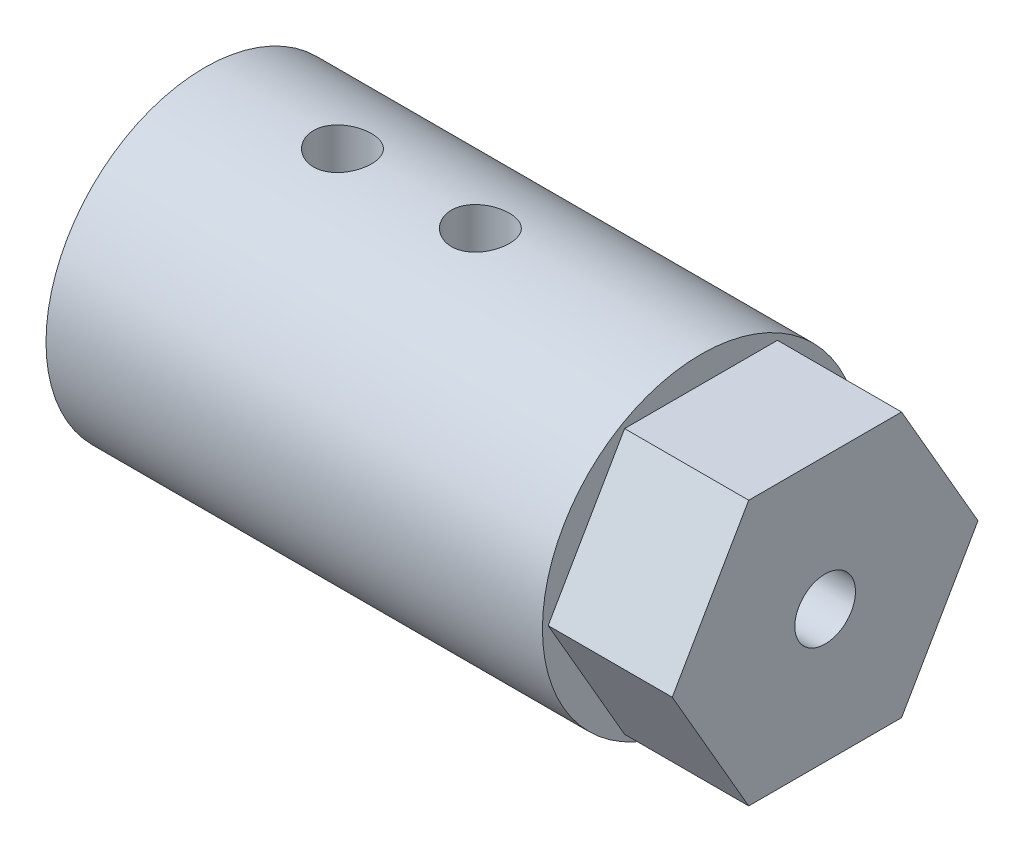
SolidWorks part; units mm, degrees
material "PLA2"
ref_plane "Front Plane" through (0, 0, 0) normal (0, 0, 1) x (1, 0, 0)
ref_plane "Top Plane" through (0, 0, 0) normal (0, 1, 0) x (1, 0, 0)
ref_plane "Right Plane" through (0, 0, 0) normal (1, 0, 0) x (0, 0, -1)
sketch "Sketch1" plane through (0, 0, 0) normal (1, 0, 0) x (0, 0, -1)
  line L0 (0, 0) -> (50000, 0) construction
  line L1 (-3.5195, 6.096) -> (3.5195, 6.096)
  line L2 (3.5195, 6.096) -> (7.0391, 0)
  line L3 (0, 0) -> (0, 50000) construction
  line L4 (-3.5195, 6.096) -> (-7.0391, 0)
  line L5 (-3.5195, -6.096) -> (-7.0391, 0)
  line L6 (3.5195, -6.096) -> (7.0391, 0)
  line L7 (-3.5195, -6.096) -> (3.5195, -6.096)
  point P8 (0, 6.096)
  point P13 (0, -6.096)
  dimension "D1" = 12.192
  dimension "D2" = 12.192
extrude "Hex" add sketch "Sketch1" along normal blind 5.715
sketch "Sketch2" plane through (0, 0, 0) normal (-1, 0, 0) x (0, 0, 1)
  circle A0 centre (0, 0) radius 7.3025
  circle A1 centre (0, 0) radius 3.2766
  dimension "D1" = 6.5532
  dimension "D2" = 14.605
extrude "Rotary_Shaft" add sketch "Sketch2" along normal blind 22.86
fillet "Fillet1" [suppressed] radius 0.889
fillet "Fillet2" [suppressed] radius 0.508
fillet "Fillet3" [suppressed] radius 0.508
sketch "Sketch3" plane through (0, 0, 0) normal (0, 1, 0) x (1, 0, 0)
  line L0 (-22.86, -7.3025) -> (0, -7.3025) construction
  line L1 (-22.86, 7.3025) -> (-22.86, -7.3025) construction
  line L2 (0, 7.3025) -> (-22.86, 7.3025) construction
  line L3 (-22.86, -7.3025) -> (0, -7.3025) construction
  line L4 (-22.86, 7.3025) -> (-22.86, -7.3025) construction
  line L5 (0, 7.3025) -> (-22.86, 7.3025) construction
  line L6 (-22.86, 0) -> (0, 0) construction
  circle A0 centre (-16.51, 0) radius 1.3335
  circle A1 centre (-10.16, 0) radius 1.3335
  dimension "D1" = 2.667
  dimension "D2" = 2.667
  dimension "D3" = 6.35
  dimension "D4" = 6.35
extrude "Cut-Extrude1" cut sketch "Sketch3" along normal through all
sketch "Sketch4" plane through (0, 0, 0) normal (-1, 0, 0) x (0, 0, 1)
  circle A0 centre (0, 0) radius 1.397
  dimension "D1" = 2.794
extrude "Cut-Extrude2" cut sketch "Sketch4" against normal through all
equation "\"D4@Sketch3\"=\"D3@Sketch3\""
equation "\"D2@Sketch3\"=\"D1@Sketch3\""
equation "\"D2@Sketch1\"=\"D1@Sketch1\""
